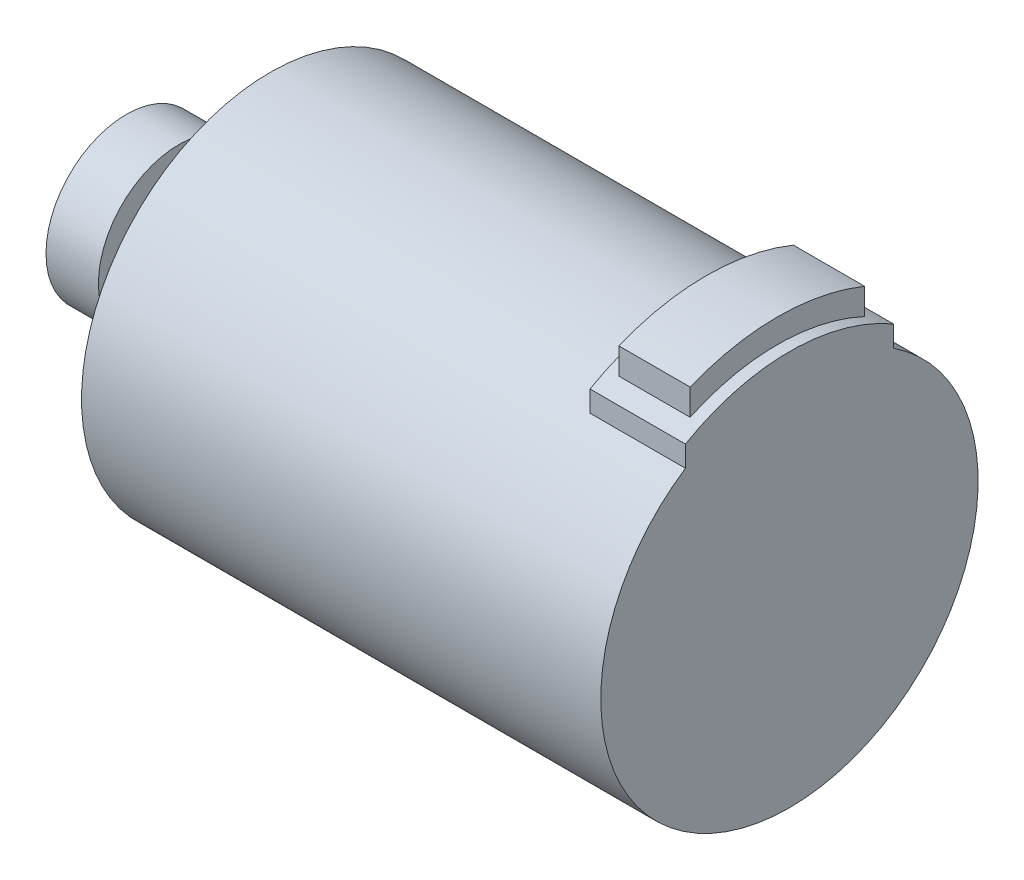
SolidWorks part; units mm, degrees
note: The reader was unsure of these and kept them because the rebuilt part matched: shared geometry of "Schizzo10<4>".
ref_plane "Piano frontale" through (0, 0, 0) normal (0, 0, 1) x (1, 0, 0)
ref_plane "Piano superiore" through (0, 0, 0) normal (0, 1, 0) x (1, 0, 0)
ref_plane "Piano destro" through (0, 0, 0) normal (1, 0, 0) x (0, 0, -1)
sketch "Schizzo1" plane through (0, 0, 0) normal (1, 0, 0) x (0, 0, -1)
  circle A0 centre (0, 0) radius 18
  dimension "D1" = 36
extrude "Estrusione-Estrusione1" add sketch "Schizzo1" along normal blind 49.54
sketch "Schizzo2" plane through (0, 0, 0) normal (-1, 0, 0) x (0, 0, 1)
  circle A0 centre (0, 0) radius 2.495
  dimension "D1" = 4.99
extrude "Estrusione-Estrusione2" add sketch "Schizzo2" along normal blind 2.5
sketch "Schizzo3" plane through (-2.5, 0, 0) normal (-1, 0, 0) x (0, 0, 1)
  circle A0 centre (0, 0) radius 1.575
  dimension "D1" = 3.15
extrude "Estrusione-Estrusione3" add sketch "Schizzo3" along normal blind 12.7
ref_plane "Piano1" through (-13.72, 0, 0) normal (-1, 0, 0) x (0, 0, 1)
sketch "Schizzo4" plane through (-13.72, 0, 0) normal (-1, 0, 0) x (0, 0, 1)
  circle A0 centre (0, 0) radius 7.67
  dimension "D1" = 15.34
extrude "Estrusione-Estrusione4" add sketch "Schizzo4" against normal blind 5
sketch "Schizzo5" plane through (-13.72, 0, 0) normal (-1, 0, 0) x (0, 0, 1)
  circle A0 centre (0, 0) radius 4.01
  dimension "D1" = 8.02
extrude "Estrusione-Estrusione5" add sketch "Schizzo5" against normal blind 9.03 from surface at 0 starting at face at (-13.72, 0, 7.67)
hole_wizard "Foro filettato M3x0.5-1" positions "Schizzo7" profile "Schizzo6" tap size "M3x0.5" standard "Ansi Metric"
sketch "Schizzo7" plane through (0, 0, 0) normal (-1, 0, 0) x (0, 0, 1)
  circle A1 centre (0, 0) radius 12.5 construction
  point P0 (12.5, 0)
  point P17 (6.25, -10.8253)
  point P18 (-6.25, -10.8253)
  point P19 (-12.5, 0)
  point P20 (-6.25, 10.8253)
  point P21 (6.25, 10.8253)
  point P22 (0, 0)
  dimension "D2" = 25
  dimension "D1" = 6
sketch "Schizzo6" plane through (0, 0, 12.5) normal (0, 1, 0) x (0, 0, 1)
  line L0 (0, 0) -> (0, 9.7511)
  line L1 (0, 9.7511) -> (1.25, 9)
  line L2 (1.25, 9) -> (1.25, 0)
  line L5 (1.25, 0) -> (0, 0)
  line L10 (0, 9.7511) -> (-1.25, 9) construction
  line L11 (0, -6.35) -> (0, 107.95) construction
  dimension "Tap Drill Dia." = 2.5
  dimension "Tap Drill Depth" = 9
  dimension "Drill Angle" = 118
cosmetic thread "Filettatura del foro1" parameters "D1"=8, "D2"=3
cosmetic thread "Filettatura del foro2" parameters "D1"=8, "D2"=3
cosmetic thread "Filettatura del foro3" parameters "D1"=8, "D2"=3
cosmetic thread "Filettatura del foro4" parameters "D1"=8, "D2"=3
cosmetic thread "Filettatura del foro5" parameters "D1"=8, "D2"=3
cosmetic thread "Filettatura del foro6" parameters "D1"=8, "D2"=3
sketch "Schizzo10" plane through (49.54, 0, 0) normal (1, 0, 0) x (0, 0, -1)
  line L0 (0, 0) -> (0, 39.8832) construction
  line L1 (-9.925, 15.0165) -> (-9.925, 17.0165)
  line L2 (-8.325, 20.3539) -> (-8.325, 17.8539)
  line L3 (8.325, 20.3539) -> (8.325, 17.8539)
  line L4 (9.925, 15.0165) -> (9.925, 17.0165)
  circle A0 centre (0, 0) radius 18 construction
  arc A1 (-9.925, 17.0165) -> (9.925, 17.0165) centre (0, 0) cw
  arc A2 (-8.325, 20.3539) -> (8.325, 20.3539) centre (0, 0) cw
  circle A3 centre (0, 0) radius 18
  circle M1 centre (0, 0) radius 18
  dimension "D1" = 19.85
  dimension "D2" = 16.65
  dimension "D3" = 2
  dimension "D4" = 2.5
extrude "Estrusione-Estrusione6" add sketch "Schizzo10" against normal blind 9.1 contours A3 L0 A1 L1 | L0 L4 A1 M1
ref_plane "Piano2" through (44.99, 0, 0) normal (1, 0, 0) x (0, 0, -1)
extrude "Estrusione-Estrusione7" add sketch "Schizzo10<4>" along normal mid plane 6.8 from surface at -4.55 contours A1 L0 A2 L2 | L0 A1 L3 A2 starting at plane "Piano2"
sketch "Schizzo10<4>" plane through (49.54, 0, 0) normal (1, 0, 0) x (0, 0, -1) same geometry as "Schizzo10"
